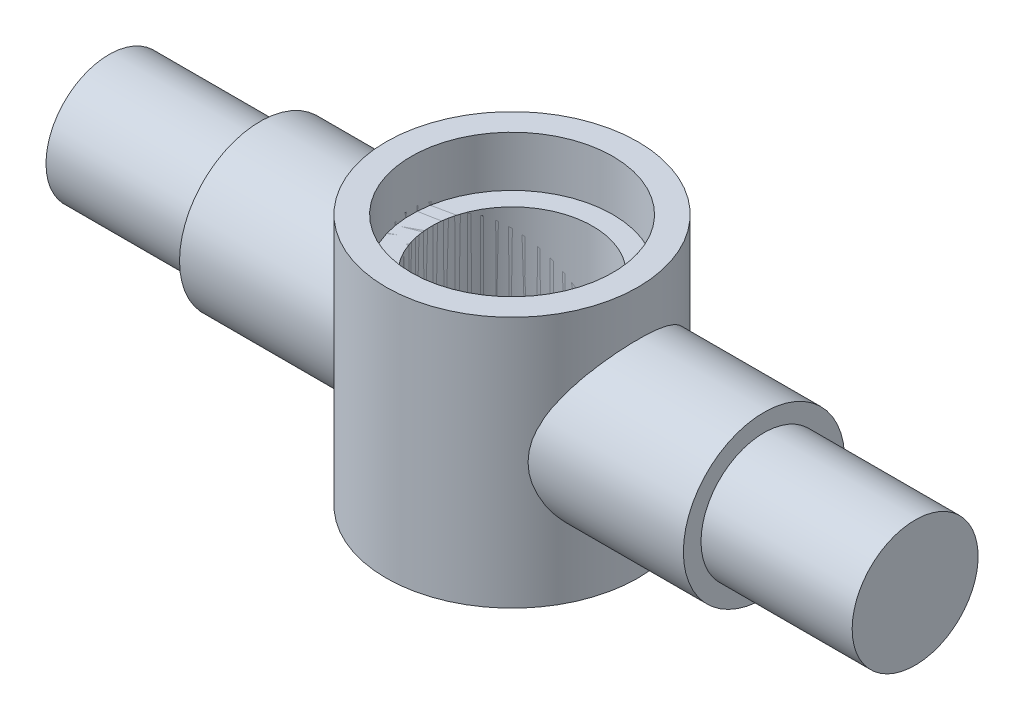
SolidWorks part; units mm, degrees
ref_plane "Front Plane" through (0, 0, 0) normal (0, 0, 1) x (1, 0, 0)
ref_plane "Top Plane" through (0, 0, 0) normal (0, 1, 0) x (1, 0, 0)
ref_plane "Right Plane" through (0, 0, 0) normal (1, 0, 0) x (0, 0, -1)
sketch "Sketch1" plane through (0, 0, 0) normal (0, 1, 0) x (1, 0, 0)
  line L0 (50, 0) -> (109.3836, 0) construction
  line L2 (-80, -12.5) -> (-50, -12.5)
  line L3 (-80, -12.5) -> (-80, 0)
  line L5 (80, -12.5) -> (80, 0)
  line L7 (50, -16) -> (50, -12.5)
  line L8 (-50, -16) -> (50, -16)
  line L9 (-50, -16) -> (-50, -12.5)
  line L12 (50, -12.5) -> (80, -12.5)
  line L13 (79.6918, 0) -> (-80, 0)
  line L14 (79.6918, 0) -> (80, 0)
  dimension "D3" = 100
  dimension "D4" = 160
revolve "Revolve2" add sketch "Sketch1" angle 360 about L0
sketch "Sketch2" plane through (0, 0, 0) normal (0, 1, 0) x (1, 0, 0)
  circle A0 centre (0, 0) radius 25
  circle A1 centre (0, 0) radius 20
  circle A2 centre (0, 0) radius 16
  dimension "D1" = 50
  dimension "D2" = 40
  dimension "D3" = 32
extrude "Boss-Extrude2" add sketch "Sketch2" along normal mid plane 50 separate body contours A1 A2 | A0 A1 region at (-24.2929, 0, 0) region at (-19.4343, 0, 0)
extrude "Cut-Extrude1" cut sketch "Sketch2<3>" against normal through all both and the other way through all contours A2 region at (0, 0, 0)
sketch "Sketch2<3>" plane through (0, 0, 0) normal (0, 1, 0) x (1, 0, 0) same geometry as "Sketch2"
sketch "Sketch3" plane through (0, 25, 0) normal (0, 1, 0) x (1, 0, 0)
  circle A0 centre (0, 0) radius 20
  dimension "D1" = 40
extrude "Cut-Extrude2" cut sketch "Sketch3" against normal blind 10
